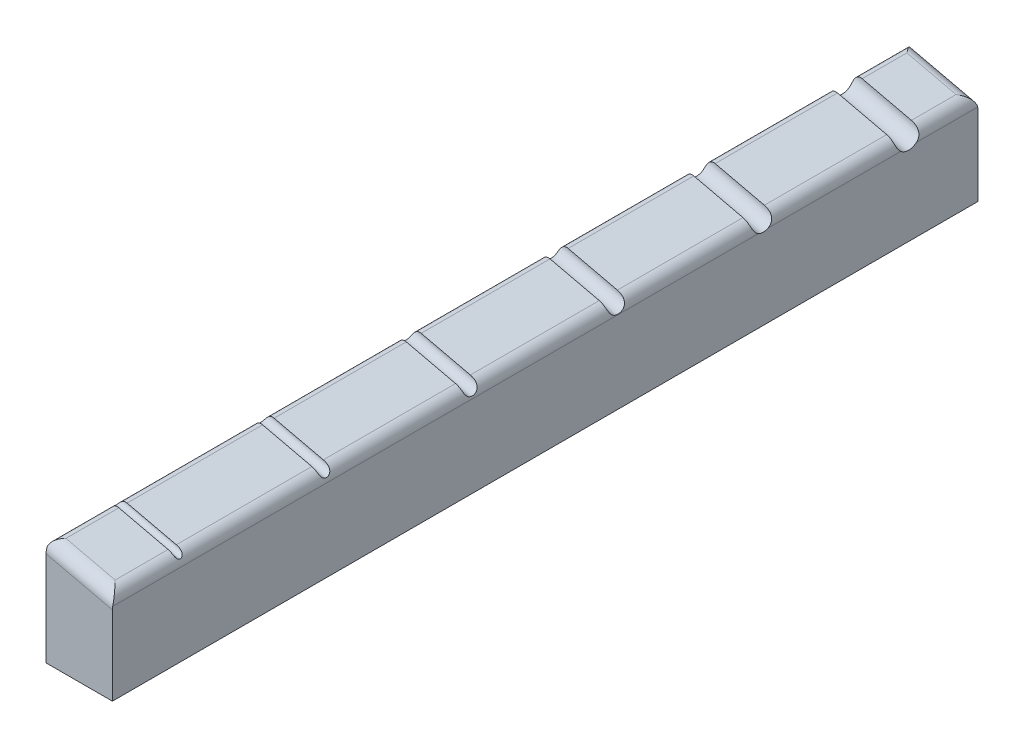
SolidWorks part; units mm, degrees
ref_plane "Front Plane" through (0, 0, 0) normal (0, 0, 1) x (1, 0, 0)
ref_plane "Top Plane" through (0, 0, 0) normal (0, 1, 0) x (1, 0, 0)
ref_plane "Right Plane" through (0, 0, 0) normal (1, 0, 0) x (0, 0, -1)
sketch "Sketch1" plane through (0, 0, 0) normal (0, 1, 0) x (1, 0, 0)
  line L1 (0, 0) -> (3.22, 0)
  line L2 (0, 0) -> (0, -41.98)
  line L3 (0, -41.98) -> (3.22, -41.98)
  line L4 (3.22, 0) -> (3.22, -41.98)
  dimension "D1" = 41.98
  dimension "D2" = 3.22
extrude "Boss-Extrude1" add sketch "Sketch1" along normal blind 5.2
sketch "Sketch2" plane through (0, 0, 41.98) normal (0, 0, 1) x (1, 0, 0)
  line L0 (0, 5.2) -> (3.22, 5.2)
  line L1 (3.22, 5.2) -> (3.22, 4.45)
  line L2 (3.22, 5.2) -> (3.22, 0) construction
  line L3 (3.22, 4.45) -> (0, 5.2)
  dimension "D1" = 0.75
extrude "Cut-Extrude1" cut sketch "Sketch2" against normal up to surface (41.98 mm away) up to face at (1.61, 2.6, 0)
sketch "Sketch3" plane through (1.1489, 4.9324, 0) normal (0.2268, 0.9739, 0) x (0.9739, -0.2268, 0)
  line L0 (-1.1796, 0) -> (-1.1796, -41.98) construction
  line L1 (-1.7391, -3.365) -> (-1.1796, -38.615) construction
  line L2 (-1.7391, -3.365) -> (3.1361, -3.365) construction
  line L3 (3.1361, -41.98) -> (3.1361, 0) construction
  line L28 (-1.7391, -10.415) -> (3.1361, -10.415) construction
  line L29 (-1.7391, -17.465) -> (3.1361, -17.465) construction
  line L30 (-1.7391, -24.515) -> (3.1361, -24.515) construction
  line L31 (-1.7391, -31.565) -> (3.1361, -31.565) construction
  line L32 (-1.7391, -38.615) -> (3.1361, -38.615) construction
  dimension "D1" = 6
ref_axis "Axis1" through (0, 5.2, 0) along (0, 0, 1)
ref_plane "Plane1" through (-1.1489, 0.2676, 0) normal (-0.9739, 0.2268, 0) x (0, 0, 1)
fillet "Fillet1" radius 0.6 3 edges at (3.22, 4.45, 20.99) (1.61, 4.825, 0) (1.61, 4.825, 41.98)
fillet "Fillet2" radius 0.3 1 edges at (0, 5.2, 20.99) tangent propagation no
sketch "Sketch4" plane through (-1.1489, 0.2676, 0) normal (-0.9739, 0.2268, 0) x (0, 0, 1)
  circle A0 centre (3.365, 5.0644) radius 0.6
  circle A1 centre (38.615, 5.0644) radius 0.2
  circle A2 centre (31.565, 5.0644) radius 0.28
  circle A3 centre (24.515, 5.0644) radius 0.36
  circle A4 centre (17.465, 5.0644) radius 0.44
  circle A5 centre (10.415, 5.0644) radius 0.52
extrude "Cut-Extrude2" cut sketch "Sketch4" against normal blind 4.98
